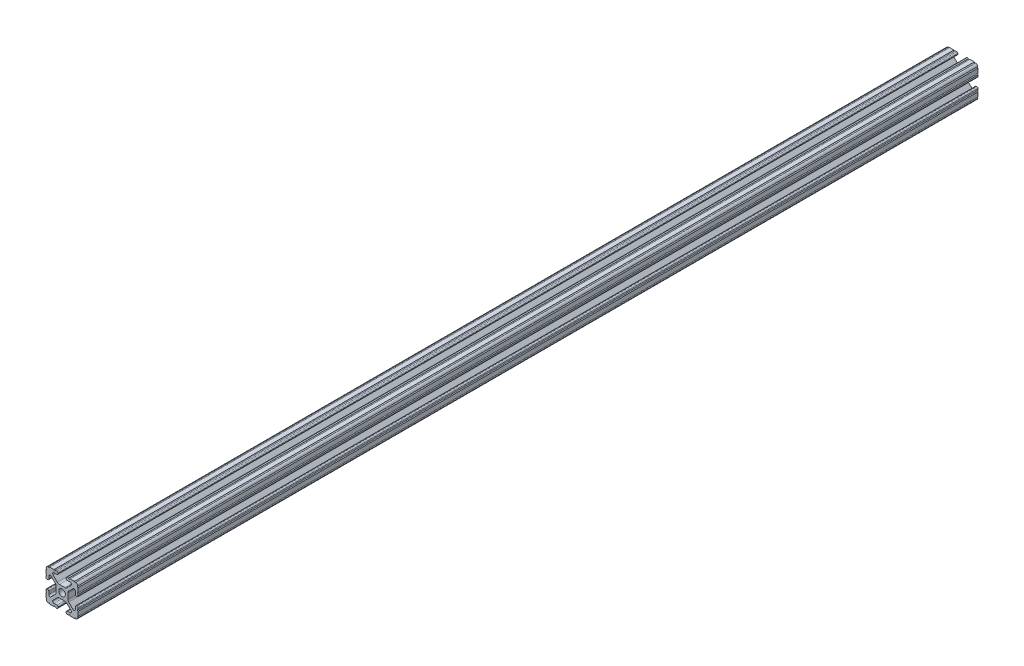
SolidWorks part; units mm, degrees
ref_plane "Front Plane" through (0, 0, 0) normal (0, 0, 1) x (1, 0, 0)
ref_plane "Top Plane" through (0, 0, 0) normal (0, 1, 0) x (1, 0, 0)
ref_plane "Right Plane" through (0, 0, 0) normal (1, 0, 0) x (0, 0, -1)
sketch "Sketch2" plane through (0, 0, 0) normal (0, 0, 1) x (1, 0, 0)
  line L0 (0, 12.7) -> (0, -12.7) construction
  line L1 (-12.7, 0) -> (12.7, 0) construction
  line L2 (3.2512, -12.7) -> (12.7, -12.7)
  line L3 (12.7, -12.7) -> (12.7, -3.2512)
  line L4 (3.2512, -12.7) -> (3.2512, -10.4902)
  line L5 (3.2512, -10.4902) -> (8.9276, -10.4902)
  line L6 (8.9276, -10.4902) -> (3.0856, -4.6482)
  line L7 (0, 0) -> (12.7, -12.7) construction
  line L8 (12.7, -3.2512) -> (10.4902, -3.2512)
  line L9 (10.4902, -3.2512) -> (10.4902, -8.9276)
  line L10 (10.4902, -8.9276) -> (4.6482, -3.0856)
  circle A0 centre (0, 0) radius 2.6035
  arc A1 (6.3485, -10.4902) -> (7.1039, -8.6665) centre (6.3485, -9.4219) ccw construction
  point P8 (0, -4.6482)
  dimension "Center Hole Diameter" = 5.207
  dimension "Rail Height" = 25.4
  dimension "Rail Width" = 25.4
  dimension "T-Slot Width" = 6.5024
  dimension "Slot Inner Width" = 14.8336
  dimension "Thickness" = 2.2098
  dimension "Slot Depth" = 5.842
  dimension "D1" = 2.2098
sketch "Sketch3" plane through (0, 0, 0) normal (1, 0, 0) x (0, 0, -1)
  line L0 (-1524, -12.7) -> (1524, -12.7) construction
  line L1 (-1498.6, 0) -> (1498.6, 0) construction
  dimension "Length" = 3048
  dimension "D1" = 25.4
sketch "Sketch4" plane through (0, 0, 0) normal (0, 0, 1) x (1, 0, 0)
  line L0 (4.1904, -12.7) -> (10.1173, -12.7)
  line L1 (3.2512, -12.7) -> (12.7, -12.7) construction
  line L2 (3.2512, -12.7) -> (3.2512, -10.4902) construction
  line L3 (3.2512, -10.4902) -> (8.9276, -10.4902) construction
  line L4 (3.2512, -11.4294) -> (3.2512, -11.7608)
  line L5 (4.1904, -10.4902) -> (6.3485, -10.4902)
  line L6 (0, -4.6482) -> (2.164, -4.6482)
  line L7 (8.9276, -10.4902) -> (3.0856, -4.6482) construction
  line L8 (3.7373, -5.2999) -> (7.1039, -8.6665)
  line L9 (12.7, -12.7) -> (12.7, -3.2512) construction
  line L10 (10.4902, -8.9276) -> (4.6482, -3.0856) construction
  line L11 (10.4902, -3.2512) -> (10.4902, -8.9276) construction
  line L12 (10.4902, -6.3485) -> (10.4902, -4.1904)
  line L13 (12.7, -3.2512) -> (10.4902, -3.2512) construction
  line L14 (11.4294, -3.2512) -> (11.7608, -3.2512)
  line L15 (12.7, -4.1904) -> (12.7, -10.1173)
  line L16 (8.6665, -7.1039) -> (5.2999, -3.7373)
  line L17 (4.6482, 0) -> (4.6482, -2.164)
  line L18 (-12.7, 0) -> (12.7, 0) construction
  line L19 (0, -4.6482) -> (0, -2.6035)
  line L20 (0, 12.7) -> (0, -12.7) construction
  line L21 (4.6482, 0) -> (2.6035, 0)
  arc A0 (3.2512, -11.7608) -> (4.1904, -12.7) centre (4.1904, -11.7608) ccw
  arc A2 (3.2512, -11.4294) -> (4.1904, -10.4902) centre (4.1904, -11.4294) cw
  arc A3 (6.3485, -10.4902) -> (7.1039, -8.6665) centre (6.3485, -9.4219) ccw
  arc A4 (2.164, -4.6482) -> (3.7373, -5.2999) centre (2.164, -6.8732) cw
  arc A5 (10.1173, -12.7) -> (12.7, -10.1173) centre (10.1173, -10.1173) ccw
  arc A6 (8.6665, -7.1039) -> (10.4902, -6.3485) centre (9.4219, -6.3485) ccw
  arc A7 (10.4902, -4.1904) -> (11.4294, -3.2512) centre (11.4294, -4.1904) cw
  arc A8 (11.7608, -3.2512) -> (12.7, -4.1904) centre (11.7608, -4.1904) cw
  arc A9 (5.2999, -3.7373) -> (4.6482, -2.164) centre (6.8732, -2.164) cw
  circle A10 centre (0, 0) radius 2.6035 construction
  arc A11 (0, -2.6035) -> (2.6035, 0) centre (0, 0) ccw
  dimension "D1" = 2.5827
  dimension "D2" = 2.225
  dimension "D3" = 0.9392
extrude "Boss-Extrude1" add sketch "Sketch4" along normal mid plane 3048
sketch "Sketch5" plane through (0, 0, 0) normal (0, 0, 1) x (1, 0, 0)
  line L0 (3.2512, -12.7) -> (12.7, -12.7) construction
  line L1 (4.1904, -10.4902) -> (6.3485, -10.4902) construction
  line L3 (0, 0) -> (12.7, -12.7) construction
  line L4 (6.3485, -10.4902) -> (6.3485, -12.7) construction
  line L5 (8.9276, -10.4902) -> (3.0856, -4.6482) construction
  circle A0 centre (10.3562, -12.7) radius 0.5524
  circle A1 centre (5.796, -12.7) radius 0.5524
  circle A2 centre (12.7, -10.3562) radius 0.5524
  circle A3 centre (12.7, -5.796) radius 0.5524
  point P10 (5.2694, -10.4902)
  point P12 (9.4219, -6.3485)
  dimension "D1" = 1.1049
extrude "Cut-Extrude1" cut sketch "Sketch5" against normal through all both and the other way through all
mirror "Mirror1" about plane through (0, 0, 0) normal (1, 0, 0) of bodies 137 134
mirror "Mirror2" about plane through (0, 0, 0) normal (0, 1, 0) of bodies 135
sketch "Sketch8" plane through (0, 0, 0) normal (0, 1, 0) x (1, 0, 0)
  line L0 (-12.58, 1524) -> (-12.58, -1524) construction
  line L1 (-25.28, 1536.7) -> (25.28, 1536.7)
  line L2 (-25.28, 1536.7) -> (-25.28, 304.8)
  line L3 (-25.28, 304.8) -> (25.28, 304.8)
  line L4 (25.28, 1536.7) -> (25.28, 304.8)
  line L5 (12.58, 1524) -> (12.58, -1524) construction
  line L6 (-6.3485, 1524) -> (-9.8037, 1524) construction
  dimension "D1" = 12.7
  dimension "D2" = 12.7
  dimension "D3" = 12.7
  dimension "D4" = 1219.2
extrude "Cut-Extrude2" cut sketch "Sketch8" against normal through all both and the other way through all
sketch "Sketch9" plane through (0, 0, 0) normal (0, 1, 0) x (1, 0, 0)
  line L0 (6.3485, -1524) -> (9.8037, -1524) construction
  line L1 (-25.4, 317.5) -> (25.28, 317.5)
  line L2 (-25.4, 317.5) -> (-25.4, -812.8)
  line L3 (-25.4, -812.8) -> (25.28, -812.8)
  line L4 (25.28, 317.5) -> (25.28, -812.8)
  line L5 (-9.8037, 304.8) -> (-6.3485, 304.8) construction
  line L7 (-12.7, 304.8) -> (-12.7, -1524) construction
  line L8 (12.58, 304.8) -> (12.58, -1524) construction
  dimension "D1" = 711.2
  dimension "D2" = 12.7
  dimension "D3" = 12.7
  dimension "D4" = 12.7
extrude "Cut-Extrude3" cut sketch "Sketch9" against normal through all both and the other way through all
equation "\"D1@Boss-Extrude1\"=\"Length@Sketch3\""
equation "\"D1@Sketch2\"=\"Thickness@Sketch2\""
equation "\"D2@Sketch4\"=\"Slot Inner Width@Sketch2\"*0.15"
equation "\"D1@Sketch4\"=\"D3@Sketch4\"*2.75"
equation "\"D3@Sketch4\"=\"Thickness@Sketch2\"*0.425"
equation "\"D1@Sketch5\"=\"Thickness@Sketch2\"*0.5"
